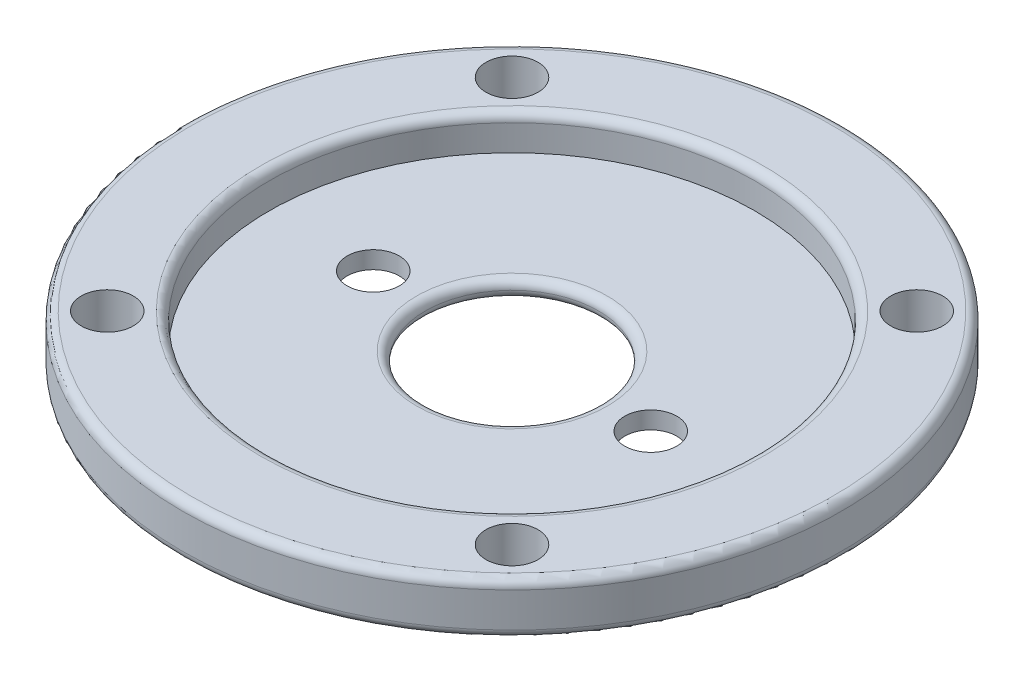
SolidWorks part; units mm, degrees
ref_plane "Front Plane" through (0, 0, 0) normal (0, 0, 1) x (1, 0, 0)
ref_plane "Top Plane" through (0, 0, 0) normal (0, 1, 0) x (1, 0, 0)
ref_plane "Right Plane" through (0, 0, 0) normal (1, 0, 0) x (0, 0, -1)
sketch "Sketch1" plane through (0, 0, 0) normal (0, 0, 1) x (1, 0, 0)
  line L0 (0, 44.0237) -> (0, -24.7716) construction
  line L1 (5, 0) -> (19, 0)
  line L2 (5, 0) -> (5, 1)
  line L3 (5, 1) -> (19, 1)
  line L4 (19, 0) -> (19, 1)
  line L5 (14, 1) -> (19, 1)
  line L6 (14, 1) -> (14, 3)
  line L7 (14, 3) -> (19, 3)
  line L8 (19, 1) -> (19, 3)
  point P10 (0, 0)
  dimension "D1" = 38
  dimension "D2" = 10
  dimension "D3" = 1
  dimension "D4" = 2
  dimension "D5" = 28
revolve "Revolve1" add sketch "Sketch1" angle 360 about L0 region at (12, 0.5, 0) region at (16.5, 2, 0)
fillet "Fillet1" radius 0.5 5 edges at (0, 0, 5) (0, 1, 5) (0, 0, 19) (0, 3, 19) (0, 3, 14)
sketch "Sketch3" plane through (0, 0, 0) normal (0, 1, 0) x (1, 0, 0)
  circle A0 centre (-8, 0) radius 1.5
  circle A1 centre (8, 0) radius 1.5
  circle A2 centre (0, 0) radius 16.5 construction
  circle A3 centre (-11.6673, 11.6673) radius 1.5
  circle A4 centre (11.6673, 11.6673) radius 1.5
  circle A5 centre (11.6673, -11.6673) radius 1.5
  circle A6 centre (-11.6673, -11.6673) radius 1.5
  point P7 (0, 0)
  point P20 (0, 0)
  dimension "D1" = 3
  dimension "D4" = 33
  dimension "D5" = 3
  dimension "D2" = 8
  dimension "D3" = 2
  dimension "D6" = 4
extrude "Cut-Extrude1" cut sketch "Sketch3" along normal blind 10
